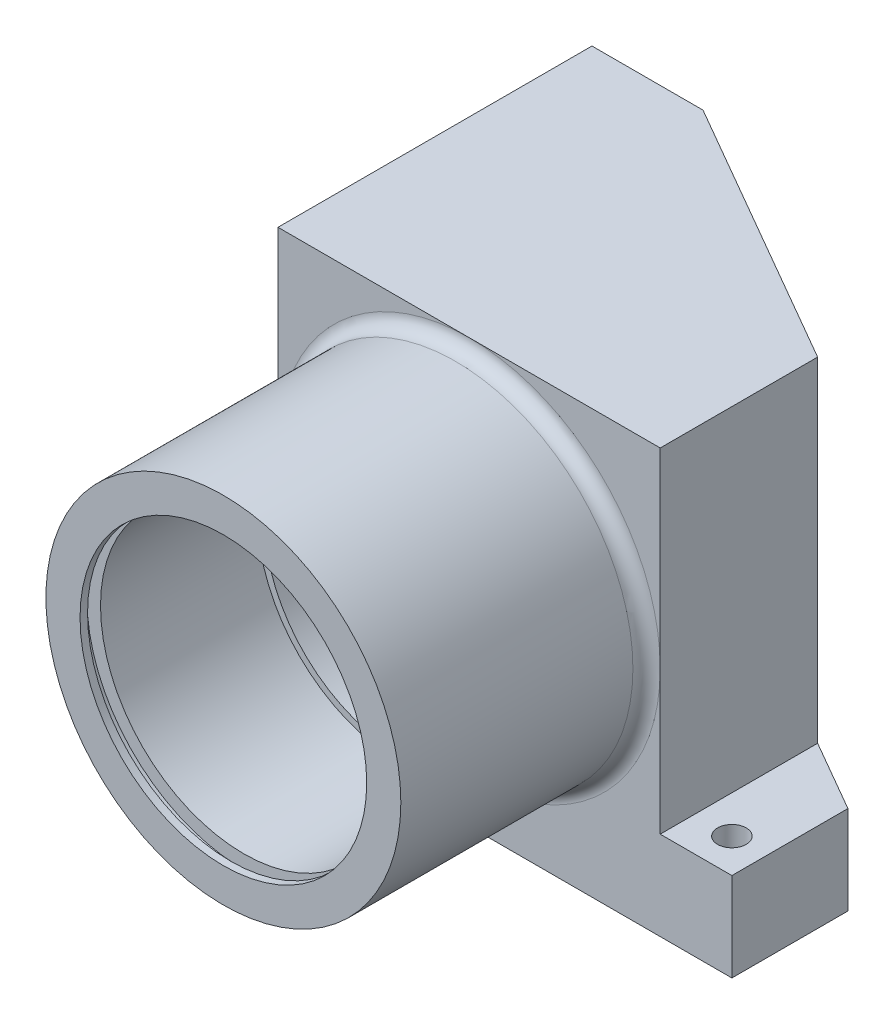
SolidWorks part; units mm, degrees
material "1060 合金"
ref_plane "前视基准面" through (0, 0, 0) normal (0, 0, 1) x (1, 0, 0)
ref_plane "上视基准面" through (0, 0, 0) normal (0, 1, 0) x (1, 0, 0)
ref_plane "右视基准面" through (0, 0, 0) normal (1, 0, 0) x (0, 0, -1)
sketch "草图1" plane through (0, 0, 0) normal (0, 0, 1) x (1, 0, 0)
  line L0 (0, -34) -> (0, 33.0223) construction
  line L1 (-28, -34) -> (28, -34)
  line L2 (-28, -34) -> (-28, 28)
  line L3 (-28, 28) -> (28, 28)
  line L4 (28, -34) -> (28, 28)
  line L5 (0, 0) -> (56.6994, 0) construction
  circle A0 centre (0, 0) radius 24 construction
  point P9 (0, 24)
  point P10 (0, -24)
  point P12 (24, 0)
  dimension "D1" = 10
  dimension "D2" = 48
  dimension "D3" = 4
  dimension "D4" = 4
extrude "凸台-拉伸1" add sketch "草图1" along normal blind 82
sketch "草图3" plane through (0, 0, 0) normal (1, 0, 0) x (0, 0, -1)
  line L0 (5.7193, 0) -> (-112.2198, 0) construction
  line L1 (0, -34) -> (0, 28) construction
  line L2 (-82, 0) -> (0, 0)
  line L3 (-82, 28) -> (-82, -34) construction
  line L4 (-82, 21) -> (-56, 21)
  line L5 (0, 0) -> (0, 23)
  line L7 (-52, 23) -> (0, 23)
  line L9 (-56, 21) -> (-56, 20)
  line L10 (-56, 20) -> (-52, 20)
  line L11 (-52, 23) -> (-52, 20)
  line L12 (-82, 0) -> (-82, 21)
  dimension "D1" = 20
  dimension "D2" = 21
  dimension "D3" = 4
  dimension "D4" = 23
  dimension "D5" = 26
revolve "切除-旋转2" cut sketch "草图3" angle 360 about L0
sketch "草图4" plane through (0, 0, 82) normal (0, 0, 1) x (1, 0, 0)
  line L0 (28, 28) -> (-28, 28) construction
  line L1 (-28, 28) -> (-28, -34) construction
  line L2 (-28, -34) -> (28, -34) construction
  line L3 (28, -34) -> (28, 28) construction
  line L4 (28, 28) -> (-28, 28)
  line L5 (-28, 28) -> (-28, -34)
  line L6 (-28, -34) -> (28, -34)
  line L7 (28, -34) -> (28, 28)
  circle A2 centre (0, 0) radius 26
  dimension "D1" = 52
chamfer "倒角1" [suppressed] distance 15 angle 45
extrude "切除-拉伸1" cut sketch "草图4" against normal blind 36
sketch "草图15" plane through (0, 0, 0) normal (0, 1, 0) x (1, 0, 0)
  line L0 (0, 0) -> (0, -98.0138) construction
  line L1 (-26, -82) -> (26, -82) construction
  line L2 (0, -80.9) -> (-23, -80.9)
  line L3 (0, -80.9) -> (0, -79)
  line L4 (0, -79) -> (-23, -79)
  line L5 (-23, -80.9) -> (-23, -79)
  dimension "D1" = 23
  dimension "D2" = 3
  dimension "D3" = 1.9
revolve "切除-旋转3" cut sketch "草图15" angle 360 about L0
fillet "圆角1" radius 2 1 edges at (26, 0, 46)
sketch "草图19" plane through (0, -34, 0) normal (0, -1, 0) x (1, 0, 0)
  line L0 (-28, 0) -> (28, 0) construction
  line L1 (-38.5, 0) -> (38.5, 0)
  line L2 (-38.5, 0) -> (-38.5, 46)
  line L3 (-38.5, 46) -> (38.5, 46)
  line L4 (38.5, 0) -> (38.5, 46)
  line L5 (-38.5, 0) -> (38.5, 46) construction
  line L6 (-38.5, 46) -> (38.5, 0) construction
  line L7 (28, 46) -> (28, 0) construction
  line L8 (28, 46) -> (-28, 46) construction
  point P0 (0, 23)
  line M2 (-28, 46) -> (-28, 0)
  line M4 (28, 0) -> (28, 46)
  dimension "D1" = 10.5
extrude "凸台-拉伸2" add sketch "草图19" against normal blind 13 contours L1 L4 L3 M4 | L3 L2 L1 M2 region at (-33.25, -34, 23) region at (33.25, -34, 23)
sketch "草图25" plane through (0, -34, 0) normal (0, -1, 0) x (1, 0, 0)
  line L0 (38.5, 29) -> (-11.7295, 0)
  line L1 (-38.5, 0) -> (38.5, 0) construction
  line L2 (-38.5, 46) -> (38.5, 46) construction
  line L3 (38.5, 0) -> (38.5, 46) construction
  dimension "D1" = 30
  dimension "D2" = 17
  dimension "D3" = 26.7705
extrude "切除-拉伸2" cut sketch "草图25" against normal through all
hole_wizard "M5 螺纹孔1" positions "草图21" profile "草图20" tap size "M5" standard "GB" end condition up to next
sketch "草图21" plane through (0, -34, 0) normal (0, -1, 0) x (-1, 0, 0)
  line L13 (0, 0) -> (0, -61.4485) construction
  line L16 (-33.5, -41) -> (33.5, -41)
  line L17 (-33.5, -41) -> (-33.5, -5)
  line L18 (-33.5, -5) -> (33.5, -5)
  line L19 (33.5, -41) -> (33.5, -5)
  line L20 (-33.5, -41) -> (33.5, -5) construction
  line L21 (-33.5, -5) -> (33.5, -41) construction
  line L22 (38.5, 0) -> (38.5, -46) construction
  line L23 (38.5, 0) -> (11.7295, 0) construction
  line L24 (38.5, -23) -> (-41.3544, -23) construction
  point P120 (33.5, -5)
  point P123 (-33.5, -41)
  point P125 (33.5, -41)
  dimension "D1" = 5
  dimension "D2" = 5
sketch "草图20" plane through (-33.5, -34, 5) normal (1, 0, 0) x (0, 0, -1)
  line L0 (0, 0) -> (0, 13)
  line L1 (0, 13) -> (2.1, 13)
  line L2 (2.1, 13) -> (2.1, 0)
  line L5 (2.1, 0) -> (0, 0)
  line L11 (0, -6.35) -> (0, 107.95) construction
  dimension "通孔螺纹孔钻头直径" = 4.2
  dimension "通孔螺纹孔钻头深度" = 13
cosmetic thread "孔螺蚊线13" parameters "D2"=5
cosmetic thread "孔螺蚊线15" parameters "D2"=5
cosmetic thread "孔螺蚊线16" parameters "D2"=5
